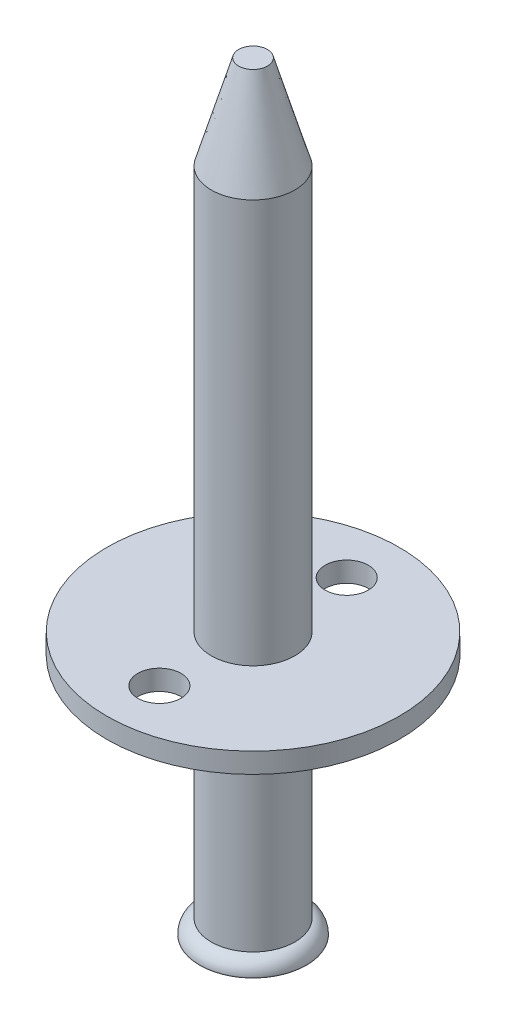
SolidWorks part; units mm, degrees
material "Alloy Steel"
ref_plane "Front Plane" through (0, 0, 0) normal (0, 0, 1) x (1, 0, 0)
ref_plane "Top Plane" through (0, 0, 0) normal (0, 1, 0) x (1, 0, 0)
ref_plane "Right Plane" through (0, 0, 0) normal (1, 0, 0) x (0, 0, -1)
sketch "Sketch1" plane through (0, 0, 0) normal (0, 1, 0) x (1, 0, 0)
  circle A0 centre (0, 0) radius 2.9
  dimension "D1" = 5.8
extrude "Boss-Extrude1" add sketch "Sketch1" along normal blind 45.2
sketch "Sketch2" plane through (0, 0, 0) normal (0, -1, 0) x (1, 0, 0)
  circle A0 centre (0, 0) radius 3.7
  point P2 (0, 0)
  dimension "D1" = 7.4
extrude "Boss-Extrude2" add sketch "Sketch2" along normal blind 1
fillet "Fillet2" radius 1 1 edges at (0, 0, -3.7)
ref_plane "Plane1" through (0, 17.2, 0) normal (0, 1, 0) x (1, 0, 0)
sketch "Sketch3" plane through (0, 17.2, 0) normal (0, 1, 0) x (1, 0, 0)
  line L0 (0, -10.15) -> (0, 10.15)
  circle A0 centre (0, 0) radius 10.15
  circle A1 centre (0, -6.5) radius 1.5
  circle A2 centre (0, 6.5) radius 1.5
  circle A3 centre (0, 0) radius 2.9 construction
  point P9 (0, 0)
  point P10 (0, 0)
  dimension "D1" = 3
  dimension "D2" = 3
  dimension "D3" = 20.3
  dimension "D4" = 13
  dimension "D5" = 6.5
extrude "Boss-Extrude3" add sketch "Sketch3" against normal blind 1.4 contours A2 L0 A1 A0 | A2 L0 A0 A1 region at (-4.4755, 17.2, 0) region at (4.4755, 17.2, 0)
ref_plane "Plane2" through (0, 51.7, 0) normal (0, 1, 0) x (1, 0, 0)
sketch "Sketch4" plane through (0, 51.7, 0) normal (0, 1, 0) x (1, 0, 0)
  circle A0 centre (0, 0) radius 1
  dimension "D1" = 2
sketch "Sketch5" plane through (0, 45.2, 0) normal (0, 1, 0) x (1, 0, 0)
  circle A0 centre (0, 0) radius 2.9
  dimension "D1" = 5.8
loft "Loft1" add profiles "Sketch4", "Sketch5" connector at (0, 51.7, 1) connector at (0, 45.2, 2.9)
